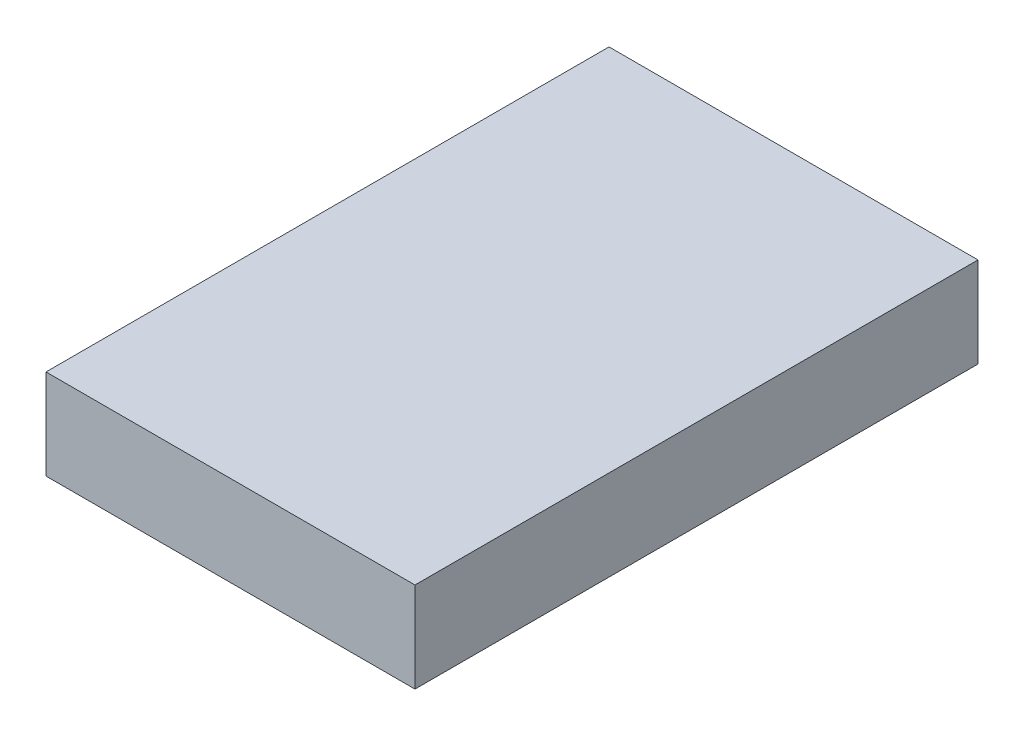
SolidWorks part; units mm, degrees
ref_plane "Front Plane" through (0, 0, 0) normal (0, 0, 1) x (1, 0, 0)
ref_plane "Top Plane" through (0, 0, 0) normal (0, 1, 0) x (1, 0, 0)
ref_plane "Right Plane" through (0, 0, 0) normal (1, 0, 0) x (0, 0, -1)
sketch "Sketch1" plane through (0, 0, 0) normal (0, 1, 0) x (1, 0, 0)
  line L1 (0, 0) -> (135, 0)
  line L2 (0, 0) -> (0, 206)
  line L3 (0, 206) -> (135, 206)
  line L4 (135, 0) -> (135, 206)
extrude "Boss-Extrude1" add sketch "Sketch1" along normal blind 33
